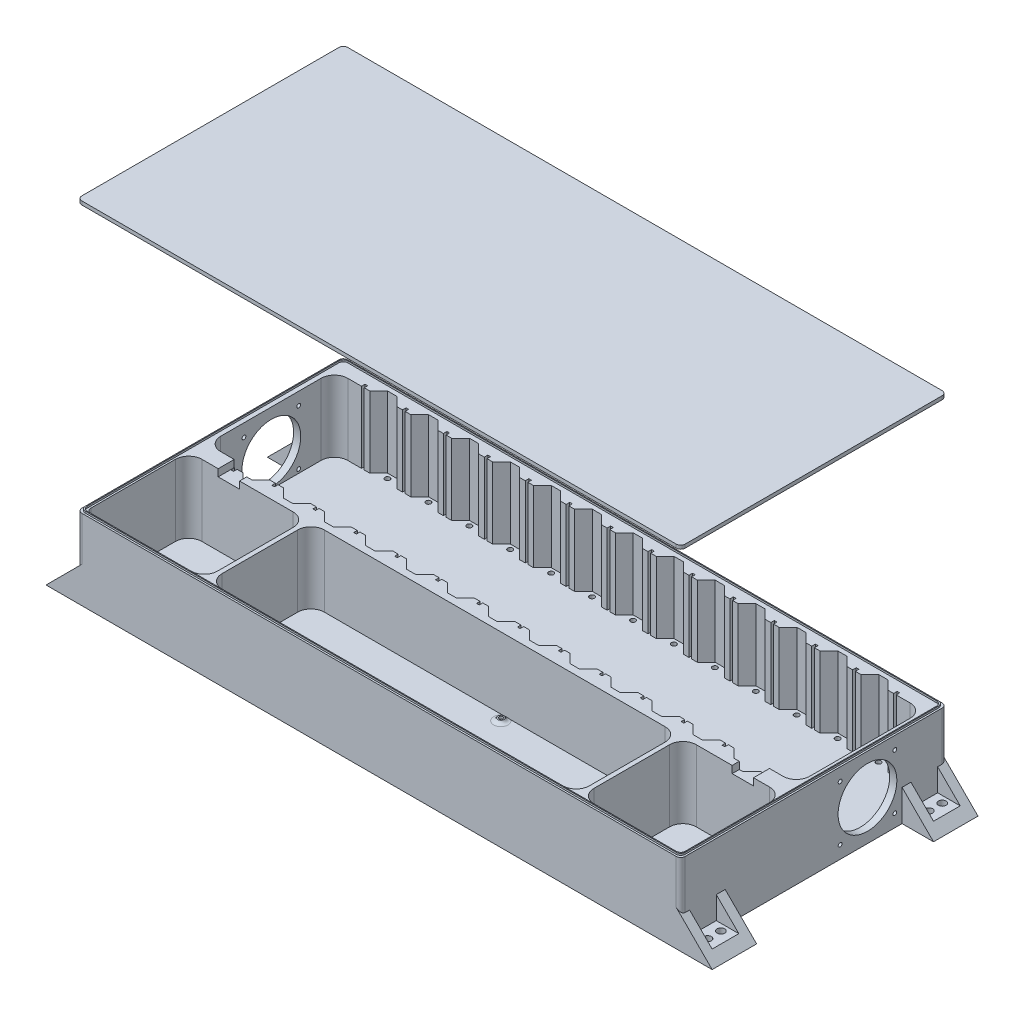
SolidWorks part; units mm, degrees
note: The reader was unsure of these and kept them because the rebuilt part matched: shared geometry of "Szkic1<8>", "Szkic1<9>", "Szkic3<4>".
ref_plane "Front Plane" through (0, 0, 0) normal (0, 0, 1) x (1, 0, 0)
ref_plane "Top Plane" through (0, 0, 0) normal (0, 1, 0) x (1, 0, 0)
ref_plane "Right Plane" through (0, 0, 0) normal (1, 0, 0) x (0, 0, -1)
sketch "Szkic1" plane through (0, 0, 0) normal (0, 1, 0) x (1, 0, 0)
  line L0 (6.5, 25) -> (-3.5, 15)
  line L1 (-11.5, 15) -> (34.5, 15)
  line L2 (-11.5, 15) -> (-11.5, -127)
  line L3 (-11.5, -127) -> (34.5, -127)
  line L4 (34.5, 15) -> (34.5, -127)
  line L5 (6.5, 15) -> (16.5, 15)
  line L6 (6.5, 15) -> (6.5, 25)
  line L7 (6.5, 25) -> (16.5, 25)
  line L8 (16.5, 15) -> (16.5, 25)
  line L9 (16.5, 25) -> (26.5, 15)
  line L10 (-11.5, 15.4) -> (-3.6657, 15.4)
  line L11 (-3.6657, 15.4) -> (6.3343, 25.4)
  line L12 (-11.5, -56) -> (-33.554, -56) construction
  line L13 (16.5, -137) -> (26.5, -127)
  line L14 (16.5, -127) -> (16.5, -137)
  line L15 (6.5, -127) -> (6.5, -137)
  line L16 (6.5, -137) -> (16.5, -137)
  line L17 (6.5, -137) -> (-3.5, -127)
  line L18 (-11.5, -155) -> (34.5, -155) [skipped]
  line L19 (-11.5, -183) -> (34.5, -183) [skipped]
  line L20 (6.3343, 25.4) -> (16.6657, 25.4)
  line L21 (16.6657, 25.4) -> (26.6657, 15.4)
  line L22 (26.6657, 15.4) -> (34.5, 15.4)
  line L23 (-11.5, 15.4) -> (-11.5, 15)
  line L24 (34.5, 15.4) -> (34.5, 15)
  line L25 (24.8809, -127.4) -> (34.5, -127.4)
  line L27 (6.3571, -137.4) -> (16.6894, -137.4)
  line L28 (-11.5, -127.4) -> (-5.8507, -127.4)
  line L30 (11.5, 15) -> (11.5, 25)
  line L31 (34.5, 15.4) -> (42.3343, 15.4)
  line L32 (42.3343, 15.4) -> (52.3343, 25.4)
  line L33 (52.3343, 25.4) -> (62.6657, 25.4)
  line L34 (62.6657, 25.4) -> (72.6657, 15.4)
  line L35 (72.6657, 15.4) -> (80.5, 15.4)
  line L36 (80.5, 15.4) -> (88.3343, 15.4)
  line L37 (88.3343, 15.4) -> (98.3343, 25.4)
  line L38 (98.3343, 25.4) -> (108.6657, 25.4)
  line L39 (108.6657, 25.4) -> (118.6657, 15.4)
  line L40 (118.6657, 15.4) -> (126.5, 15.4)
  line L41 (126.5, 15.4) -> (134.3343, 15.4)
  line L42 (134.3343, 15.4) -> (144.3343, 25.4)
  line L43 (144.3343, 25.4) -> (154.6657, 25.4)
  line L44 (154.6657, 25.4) -> (164.6657, 15.4)
  line L45 (164.6657, 15.4) -> (172.5, 15.4)
  line L46 (172.5, 15.4) -> (180.3343, 15.4)
  line L47 (180.3343, 15.4) -> (190.3343, 25.4)
  line L48 (190.3343, 25.4) -> (200.6657, 25.4)
  line L49 (200.6657, 25.4) -> (210.6657, 15.4)
  line L50 (210.6657, 15.4) -> (218.5, 15.4)
  line L51 (218.5, 15.4) -> (226.3343, 15.4)
  line L52 (226.3343, 15.4) -> (236.3343, 25.4)
  line L53 (236.3343, 25.4) -> (246.6657, 25.4)
  line L54 (246.6657, 25.4) -> (256.6657, 15.4)
  line L55 (256.6657, 15.4) -> (264.5, 15.4)
  line L56 (264.5, 15.4) -> (272.3343, 15.4)
  line L57 (272.3343, 15.4) -> (282.3343, 25.4)
  line L58 (282.3343, 25.4) -> (292.6657, 25.4)
  line L59 (292.6657, 25.4) -> (302.6657, 15.4)
  line L60 (302.6657, 15.4) -> (310.5, 15.4)
  line L61 (310.5, 15.4) -> (318.3343, 15.4)
  line L62 (318.3343, 15.4) -> (328.3343, 25.4)
  line L63 (328.3343, 25.4) -> (338.6657, 25.4)
  line L64 (338.6657, 25.4) -> (348.6657, 15.4)
  line L65 (348.6657, 15.4) -> (356.5, 15.4)
  line L66 (356.5, 15.4) -> (364.3343, 15.4)
  line L67 (364.3343, 15.4) -> (374.3343, 25.4)
  line L68 (374.3343, 25.4) -> (384.6657, 25.4)
  line L69 (384.6657, 25.4) -> (394.6657, 15.4)
  line L70 (394.6657, 15.4) -> (402.5, 15.4)
  line L71 (402.5, 15.4) -> (410.3343, 15.4)
  line L72 (410.3343, 15.4) -> (420.3343, 25.4)
  line L73 (420.3343, 25.4) -> (430.6657, 25.4)
  line L74 (430.6657, 25.4) -> (440.6657, 15.4)
  line L75 (440.6657, 15.4) -> (448.5, 15.4)
  line L76 (448.5, 15.4) -> (456.3343, 15.4)
  line L77 (456.3343, 15.4) -> (466.3343, 25.4)
  line L78 (466.3343, 25.4) -> (476.6657, 25.4)
  line L79 (476.6657, 25.4) -> (486.6657, 15.4)
  line L80 (486.6657, 15.4) -> (494.5, 15.4)
  line L81 (494.5, 15.4) -> (502.3343, 15.4)
  line L82 (502.3343, 15.4) -> (512.3343, 25.4)
  line L83 (512.3343, 25.4) -> (522.6657, 25.4)
  line L84 (522.6657, 25.4) -> (532.6657, 15.4)
  line L85 (532.6657, 15.4) -> (540.5, 15.4)
  line L86 (540.5, 15.4) -> (548.3343, 15.4)
  line L87 (548.3343, 15.4) -> (558.3343, 25.4)
  line L88 (558.3343, 25.4) -> (568.6657, 25.4)
  line L89 (568.6657, 25.4) -> (578.6657, 15.4)
  line L90 (578.6657, 15.4) -> (586.5, 15.4)
  line L91 (-11.5, -127.4) -> (-3.6657, -127.4)
  line L92 (-3.6657, -127.4) -> (6.3343, -137.4)
  line L93 (16.6657, -137.4) -> (26.6657, -127.4)
  line L94 (6.3343, -137.4) -> (16.6657, -137.4)
  line L95 (26.6657, -127.4) -> (34.5, -127.4)
  line L96 (310.5, -127.4) -> (318.3343, -127.4)
  line L97 (302.6657, -127.4) -> (310.5, -127.4)
  line L98 (292.6657, -137.4) -> (302.6657, -127.4)
  line L99 (282.3343, -137.4) -> (292.6657, -137.4)
  line L100 (272.3343, -127.4) -> (282.3343, -137.4)
  line L101 (264.5, -127.4) -> (272.3343, -127.4)
  line L102 (256.6657, -127.4) -> (264.5, -127.4)
  line L103 (246.6657, -137.4) -> (256.6657, -127.4)
  line L104 (236.3343, -137.4) -> (246.6657, -137.4)
  line L105 (226.3343, -127.4) -> (236.3343, -137.4)
  line L106 (218.5, -127.4) -> (226.3343, -127.4)
  line L107 (210.6657, -127.4) -> (218.5, -127.4)
  line L108 (200.6657, -137.4) -> (210.6657, -127.4)
  line L109 (190.3343, -137.4) -> (200.6657, -137.4)
  line L110 (180.3343, -127.4) -> (190.3343, -137.4)
  line L111 (172.5, -127.4) -> (180.3343, -127.4)
  line L112 (164.6657, -127.4) -> (172.5, -127.4)
  line L113 (154.6657, -137.4) -> (164.6657, -127.4)
  line L114 (144.3343, -137.4) -> (154.6657, -137.4)
  line L115 (134.3343, -127.4) -> (144.3343, -137.4)
  line L116 (126.5, -127.4) -> (134.3343, -127.4)
  line L117 (118.6657, -127.4) -> (126.5, -127.4)
  line L118 (108.6657, -137.4) -> (118.6657, -127.4)
  line L119 (98.3343, -137.4) -> (108.6657, -137.4)
  line L120 (88.3343, -127.4) -> (98.3343, -137.4)
  line L121 (80.5, -127.4) -> (88.3343, -127.4)
  line L122 (72.6657, -127.4) -> (80.5, -127.4)
  line L123 (62.6657, -137.4) -> (72.6657, -127.4)
  line L124 (52.3343, -137.4) -> (62.6657, -137.4)
  line L125 (42.3343, -127.4) -> (52.3343, -137.4)
  line L126 (34.5, -127.4) -> (42.3343, -127.4)
  line L127 (512.3343, -137.4) -> (522.6657, -137.4)
  line L128 (466.3343, -137.4) -> (476.6657, -137.4)
  line L129 (420.3343, -137.4) -> (430.6657, -137.4)
  line L130 (410.3343, -127.4) -> (420.3343, -137.4)
  line L131 (402.5, -127.4) -> (410.3343, -127.4)
  line L132 (394.6657, -127.4) -> (402.5, -127.4)
  line L133 (384.6657, -137.4) -> (394.6657, -127.4)
  line L134 (374.3343, -137.4) -> (384.6657, -137.4)
  line L135 (364.3343, -127.4) -> (374.3343, -137.4)
  line L136 (356.5, -127.4) -> (364.3343, -127.4)
  line L137 (348.6657, -127.4) -> (356.5, -127.4)
  line L138 (338.6657, -137.4) -> (348.6657, -127.4)
  line L139 (328.3343, -137.4) -> (338.6657, -137.4)
  line L140 (318.3343, -127.4) -> (328.3343, -137.4)
  line L141 (578.6657, -127.4) -> (586.5, -127.4)
  line L142 (568.6657, -137.4) -> (578.6657, -127.4)
  line L143 (558.3343, -137.4) -> (568.6657, -137.4)
  line L144 (548.3343, -127.4) -> (558.3343, -137.4)
  line L145 (540.5, -127.4) -> (548.3343, -127.4)
  line L146 (532.6657, -127.4) -> (540.5, -127.4)
  line L147 (522.6657, -137.4) -> (532.6657, -127.4)
  line L148 (502.3343, -127.4) -> (512.3343, -137.4)
  line L149 (494.5, -127.4) -> (502.3343, -127.4)
  line L150 (486.6657, -127.4) -> (494.5, -127.4)
  line L151 (586.5, 15.4) -> (586.5, -127.4)
  line L152 (-51.5, 33.4) -> (626.5, 33.4)
  line L153 (-51.5, 33.4) -> (-51.5, -145.4)
  line L154 (-51.5, -145.4) -> (626.5, -145.4)
  line L155 (626.5, 33.4) -> (626.5, -145.4)
  line L156 (586.5, -127.4) -> (626.5, -127.4)
  line L157 (586.5, 15.4) -> (626.5, 15.4)
  line L158 (-43.5, 15.4) -> (-43.5, -127.4)
  line L159 (618.5, 15.4) -> (618.5, -127.4)
  line L160 (586.5, -127.4) -> (586.5, -145.4)
  line L161 (-11.5, -127) -> (-11.5, -127.4)
  line L162 (-11.5, -127.4) -> (-51.5, -127.4)
  line L163 (-11.5, 15.4) -> (-51.5, 15.4)
  line L164 (476.6657, -137.4) -> (486.6657, -127.4)
  line L165 (456.3343, -127.4) -> (466.3343, -137.4)
  line L166 (448.5, -127.4) -> (456.3343, -127.4)
  line L167 (440.6657, -127.4) -> (448.5, -127.4)
  line L168 (430.6657, -137.4) -> (440.6657, -127.4)
  circle A0 centre (0, 0) radius 8.25
  circle A1 centre (0, 0) radius 10.6
  circle A2 centre (0, 0) radius 10.1
  circle A3 centre (0, 0) radius 11
  circle A5 centre (23, 0) radius 8.25
  circle A6 centre (23, 0) radius 10.6
  circle A7 centre (23, 0) radius 10.1
  circle A8 centre (23, 0) radius 11
  circle A10 centre (23, -28) radius 8.25
  circle A11 centre (23, -28) radius 10.6
  circle A12 centre (23, -28) radius 10.1
  circle A13 centre (23, -28) radius 11
  circle A15 centre (0, -28) radius 8.25
  circle A16 centre (0, -28) radius 10.6
  circle A17 centre (0, -28) radius 10.1
  circle A18 centre (0, -28) radius 11
  circle A20 centre (0, -56) radius 11
  circle A21 centre (0, -56) radius 10.6
  circle A22 centre (0, -56) radius 10.1
  circle A23 centre (0, -56) radius 8.25
  circle A24 centre (23, -56) radius 8.25
  circle A25 centre (23, -56) radius 10.1
  circle A26 centre (23, -56) radius 10.6
  circle A27 centre (23, -56) radius 11
  circle A28 centre (0, -84) radius 11
  circle A29 centre (0, -84) radius 10.6
  circle A30 centre (0, -84) radius 10.1
  circle A31 centre (0, -84) radius 8.25
  circle A32 centre (23, -84) radius 8.25
  circle A33 centre (23, -84) radius 10.1
  circle A34 centre (23, -84) radius 10.6
  circle A35 centre (23, -84) radius 11
  circle A36 centre (0, -112) radius 11
  circle A37 centre (0, -112) radius 10.6
  circle A38 centre (0, -112) radius 10.1
  circle A39 centre (0, -112) radius 8.25
  circle A40 centre (23, -112) radius 8.25
  circle A41 centre (23, -112) radius 10.1
  circle A42 centre (23, -112) radius 10.6
  circle A43 centre (23, -112) radius 11
  circle A44 centre (11.5, 20) radius 2.8
  circle A45 centre (11.5, -132) radius 2.8
  circle A46 centre (57.5, 20) radius 2.8
  circle A47 centre (103.5, 20) radius 2.8
  circle A48 centre (149.5, 20) radius 2.8
  circle A49 centre (195.5, 20) radius 2.8
  circle A50 centre (241.5, 20) radius 2.8
  circle A51 centre (287.5, 20) radius 2.8
  circle A52 centre (333.5, 20) radius 2.8
  circle A53 centre (379.5, 20) radius 2.8
  circle A54 centre (425.5, 20) radius 2.8
  circle A55 centre (471.5, 20) radius 2.8
  circle A56 centre (517.5, 20) radius 2.8
  circle A57 centre (563.5, 20) radius 2.8
  circle A58 centre (287.5, -132) radius 2.8
  circle A59 centre (241.5, -132) radius 2.8
  circle A60 centre (195.5, -132) radius 2.8
  circle A61 centre (149.5, -132) radius 2.8
  circle A62 centre (103.5, -132) radius 2.8
  circle A63 centre (57.5, -132) radius 2.8
  circle A64 centre (425.5, -132) radius 2.8
  circle A65 centre (379.5, -132) radius 2.8
  circle A66 centre (333.5, -132) radius 2.8
  circle A67 centre (563.5, -132) radius 2.8
  circle A68 centre (517.5, -132) radius 2.8
  circle A69 centre (471.5, -132) radius 2.8
  dimension "D1" = 16.5
  dimension "D2" = 20.2
  dimension "D3" = 21.2
  dimension "D4" = 0.4
  dimension "D5" = 23
  dimension "D8" = 11.5
  dimension "D10" = 2
  dimension "D22" = 5.6
  dimension "D9" = 11.5
  dimension "D11" = 15
  dimension "D12" = 10
  dimension "D13" = 18
  dimension "D14" = 10
  dimension "D15" = 3
  dimension "D16" = 15
  dimension "D17" = 0.4
  dimension "D18" = 45
  dimension "D19" = 45
  dimension "D20" = 0.4
  dimension "D21" = 0.4
  dimension "D23" = 0.4
  dimension "D25" = 0.4
  dimension "D26" = 40
  dimension "D27" = 40
  dimension "D28" = 8
  dimension "D29" = 8
  dimension "D6" = 2
  dimension "D7" = 2
extrude "Dodanie-wyciągnięcie1" add sketch "Szkic1" along normal blind 10
extrude "Dodanie-wyciągnięcie2" add sketch "Szkic1<8>" along normal blind 80 from surface at 10 starting at face at (287.5, 10, 56)
sketch "Szkic1<8>" plane through (0, 0, 0) normal (0, 1, 0) x (1, 0, 0) same geometry as "Szkic1"
extrude "Wytnij-wyciągnięcie2" cut sketch "Szkic1<9>" against normal blind 5 from surface contours A46 | A47 | A48 | A49 | A61 | A60 | A50 | A51 | A58 | A66 | A65 | A52 | A53 | A54 | A55 | A64 | A67 | A57 | A56
sketch "Szkic1<9>" plane through (0, 0, 0) normal (0, 1, 0) x (1, 0, 0) same geometry as "Szkic1"
sketch "Szkic2" plane through (-51.5, 0, 0) normal (-1, 0, 0) x (0, 0, 1)
  line L0 (-33.4, 0) -> (145.4, 0) construction
  circle A1 centre (24.7303, 75.747) radius 2.15
  circle A2 centre (24.7303, 14.247) radius 2.15
  circle A3 centre (86.2303, 14.247) radius 2.15
  circle A4 centre (86.2303, 75.747) radius 2.15
  circle A5 centre (55.4803, 44.997) radius 33.0377
  point P2 (56, 0)
  point P5 (22.0807, 90.9367)
  dimension "D3" = 43.4871
  dimension "D4" = 66.0755
  dimension "D1" = 43.4871
  dimension "D2" = 43.4871
  dimension "D5" = 43.4871
  dimension "D6" = 45
extrude "Wytnij-wyciągnięcie3" cut sketch "Szkic2" against normal blind 800
sketch "Szkic3" plane through (0, 0, 0) normal (0, -1, 0) x (1, 0, 0)
  line L0 (626.5, -33.4) -> (626.5, 145.4) construction
  line L1 (-51.5, 145.4) -> (626.5, 145.4)
  line L2 (-51.5, 145.4) -> (-51.5, 265.4)
  line L3 (-51.5, 265.4) -> (626.5, 265.4)
  line L4 (626.5, 145.4) -> (626.5, 265.4)
  line L5 (-46.5, 260.4) -> (621.5, 260.4)
  line L6 (-46.5, 260.4) -> (-46.5, 145.4)
  line L7 (-46.5, 145.4) -> (621.5, 145.4)
  line L8 (621.5, 260.4) -> (621.5, 145.4)
  line M6 (626.5, 145.4) -> (-51.5, 145.4)
  dimension "D1" = 120
  dimension "D2" = 5
  dimension "D3" = 0
  dimension "D4" = 5
  dimension "D5" = 5
extrude "Dodanie-wyciągnięcie3" add sketch "Szkic3" against normal up to surface (10 mm away) contours L5 L8 L4 L3 L2 L1 L6 M6 | L8 L5 L6 L1
extrude "Dodanie-wyciągnięcie4" add sketch "Szkic3<4>" against normal up to surface (90 mm away) contours L5 L8 L4 L3 L2 L1 L6 M6 up to face at (287.5, 90, 56)
sketch "Szkic3<4>" plane through (0, 0, 0) normal (0, -1, 0) x (1, 0, 0) same geometry as "Szkic3"
ref_plane "Płaszczyzna1" through (287.5, 0, 0) normal (-1, 0, 0) x (0, 0, 1)
sketch "Szkic5" plane through (0, 0, 265.4) normal (0, 0, 1) x (1, 0, 0)
  line L0 (-51.5, 0) -> (-86.8553, 0)
  line L1 (-86.8553, 0) -> (-51.5, 35.3553)
  line L2 (-51.5, 90) -> (-51.5, 0) construction
  line L3 (-51.5, 35.3553) -> (-51.5, 0)
  dimension "D1" = 50
extrude "Dodanie-wyciągnięcie5" add sketch "Szkic5" against normal blind 50
sketch "Szkic6" plane through (-51.5, 0, 0) normal (-1, 0, 0) x (0, 0, 1)
  line L0 (215.4, 35.3553) -> (265.4, 35.3553) construction
  line L1 (225.4, 35.3553) -> (255.4, 35.3553)
  line L2 (225.4, 35.3553) -> (225.4, 10)
  line L3 (225.4, 10) -> (255.4, 10)
  line L4 (255.4, 35.3553) -> (255.4, 10)
  line L5 (215.4, 35.3553) -> (215.4, 0) construction
  line L6 (265.4, 35.3553) -> (265.4, 0) construction
  line L7 (215.4, 0) -> (265.4, 0) construction
  dimension "D1" = 10
  dimension "D2" = 10
  dimension "D3" = 10
extrude "Wytnij-wyciągnięcie4" cut sketch "Szkic6" along normal blind 40
sketch "Szkic7" plane through (0, 10, 0) normal (0, 1, 0) x (1, 0, 0)
  line L0 (-64.1777, -255.4) -> (-64.1777, -225.4)
  line L1 (-76.8553, -255.4) -> (-51.5, -255.4) construction
  line L3 (-59.9277, -240.4) -> (-59.9277, -225.4)
  line L4 (-59.9277, -240.4) -> (-59.9277, -255.4)
  line L6 (-51.5, -255.4) -> (-76.8553, -255.4) construction
  circle A3 centre (-64.1777, -232.9) radius 4.25
  circle A4 centre (-64.1777, -247.9) radius 4.25
  dimension "D1" = 8.5
  dimension "D2" = 8.5
extrude "Wytnij-wyciągnięcie5" cut sketch "Szkic7" against normal blind 40 contours L0 A4 | L0 A4 | L0 A3 | L0 A3
ref_plane "Płaszczyzna2" through (0, 0, 116) normal (0, 0, 1) x (1, 0, 0)
mirror "Lustro1" about plane through (287.5, 0, 0) normal (-1, 0, 0) of "Wytnij-wyciągnięcie4", "Dodanie-wyciągnięcie5", "Wytnij-wyciągnięcie5" second plane through (0, 0, 116) second plane normal (0, 0, 1)
sketch "Szkic9" plane through (0, 10, 0) normal (0, 1, 0) x (1, 0, 0)
  line L0 (506.5, -145.4) -> (506.5, -260.4)
  line L1 (621.5, -145.4) -> (-46.5, -145.4) construction
  line L2 (621.5, -260.4) -> (-46.5, -260.4) construction
  line L3 (88.5, -145.4) -> (88.5, -260.4)
  line L4 (621.5, -145.4) -> (-46.5, -145.4) construction
  line L5 (621.5, -260.4) -> (-46.5, -260.4) construction
  line L6 (-51.5, -265.4) -> (-51.5, 33.4) construction
  line L7 (626.5, -265.4) -> (626.5, 33.4) construction
  dimension "D1" = 140
  dimension "D2" = 120
extrude "Wyciągnięcie-cienka ścianka1" add sketch "Szkic9" along normal up to surface (80 mm away) thin up to face at (287.5, 90, 202.9) thin type mid plane wall 5
sketch "Szkic8" plane through (0, 10, 0) normal (0, 1, 0) x (1, 0, 0)
  circle A0 centre (452.5969, -151.7073) radius 2.1
  circle A1 centre (452.6219, -219.6823) radius 2.1
  circle A2 centre (310.9469, -151.9823) radius 2.1
  circle A3 centre (310.4051, -200.749) radius 2.1
  circle A4 centre (331.8636, -254.5905) radius 2.1
  circle A5 centre (310.9469, -151.9823) radius 3.5
  circle A6 centre (452.5969, -151.7073) radius 3.5
  circle A7 centre (452.6219, -219.6823) radius 3.5
  circle A8 centre (331.8636, -254.5905) radius 3.5
  circle A9 centre (310.4051, -200.749) radius 3.5
  dimension "D1" = 7
  dimension "D2" = 7
  dimension "D3" = 7
  dimension "D4" = 7
  dimension "D5" = 7
  dimension "D6" = 4.2
  dimension "D7" = 4.2
  dimension "D8" = 4.2
  dimension "D9" = 4.2
  dimension "D10" = 4.2
extrude "Dodanie-wyciągnięcie6" add sketch "Szkic8" along normal blind 3
fillet "Zaokrąglenie2" radius 5 5 edges at (331.8636, 10, 258.0905) (452.6219, 10, 223.1823) (452.5969, 10, 155.2073) (310.4051, 10, 204.249) (310.9469, 10, 155.4823)
sketch "Szkic10" plane through (0, 90, 0) normal (0, 1, 0) x (1, 0, 0)
  line L0 (-49, 30.9) -> (624, 30.9)
  line L2 (624, 30.9) -> (624, -262.9)
  line L3 (624, -262.9) -> (-49, -262.9)
  line L4 (-49, -262.9) -> (-49, 30.9)
  line L5 (626.5, 33.4) -> (-51.5, 33.4) construction
  line L6 (-51.5, -265.4) -> (-51.5, 33.4) construction
  line L7 (-51.5, -265.4) -> (626.5, -265.4) construction
  line L8 (626.5, -265.4) -> (626.5, 33.4) construction
  point P0 (624.4868, 27.7695)
  point P4 (0, 0)
  point P7 (-49.386, 27.672)
  dimension "D1" = 2.5
  dimension "D2" = 2.5
  dimension "D3" = 2.5
  dimension "D4" = 2.5
extrude "Wyciągnięcie-cienka ścianka2" add sketch "Szkic10" along normal blind 2 thin thin type mid plane wall 1
sketch "Szkic14" plane through (0, 90, 0) normal (0, 1, 0) x (1, 0, 0)
  line L0 (34.5, 15.4) -> (34.5, 19.4)
  line L1 (42.3343, 15.4) -> (26.6657, 15.4) construction
  line L2 (80.5, 15.4) -> (80.5, 19.4)
  line L3 (126.5, 15.4) -> (126.5, 19.4)
  line L4 (172.5, 15.4) -> (172.5, 19.4)
  line L5 (218.5, 15.4) -> (218.5, 19.4)
  line L6 (264.5, 15.4) -> (264.5, 19.4)
  line L7 (310.5, 15.4) -> (310.5, 19.4)
  line L8 (356.5, 15.4) -> (356.5, 19.4)
  line L9 (402.5, 15.4) -> (402.5, 19.4)
  line L10 (448.5, 15.4) -> (448.5, 19.4)
  line L11 (494.5, 15.4) -> (494.5, 19.4)
  line L12 (540.5, 15.4) -> (540.5, 19.4)
  line L13 (586.5, 15.4) -> (586.5, 19.4)
  line L14 (-11.5, 15.4) -> (-11.5, 19.4)
  line L15 (-43.5, -56) -> (-26.8479, -56) construction
  line L16 (-43.5, -127.4) -> (-43.5, 15.4) construction
  line L17 (-11.5, -127.4) -> (-11.5, -131.4)
  line L18 (586.5, -127.4) -> (586.5, -131.4)
  line L19 (540.5, -127.4) -> (540.5, -131.4)
  line L20 (494.5, -127.4) -> (494.5, -131.4)
  line L21 (448.5, -127.4) -> (448.5, -131.4)
  line L22 (402.5, -127.4) -> (402.5, -131.4)
  line L23 (356.5, -127.4) -> (356.5, -131.4)
  line L24 (310.5, -127.4) -> (310.5, -131.4)
  line L25 (264.5, -127.4) -> (264.5, -131.4)
  line L26 (218.5, -127.4) -> (218.5, -131.4)
  line L27 (172.5, -127.4) -> (172.5, -131.4)
  line L28 (126.5, -127.4) -> (126.5, -131.4)
  line L29 (80.5, -127.4) -> (80.5, -131.4)
  line L30 (34.5, -127.4) -> (34.5, -131.4)
  dimension "D1" = 4
  dimension "D2" = 13
  dimension "D3" = 2
extrude "Wycięcie-wyciągnięcie-cienka ścianka2" cut sketch "Szkic14" against normal up to surface (80 mm away) thin thin type mid plane wall 3
ref_plane "Płaszczyzna3" through (0, 390, 0) normal (0, 1, 0) x (1, 0, 0)
sketch "Szkic11" plane through (0, 390, 0) normal (0, 1, 0) x (1, 0, 0)
  line L1 (-51.5, 33.4) -> (626.5, 33.4)
  line L2 (-51.5, 33.4) -> (-51.5, -265.4)
  line L3 (-51.5, -265.4) -> (626.5, -265.4)
  line L4 (626.5, 33.4) -> (626.5, -265.4)
extrude "Dodanie-wyciągnięcie7" add sketch "Szkic11" along normal blind 4 separate body
sketch "Szkic12" plane through (0, 390, 0) normal (0, 1, 0) x (1, 0, 0)
  line L0 (-49, 30.9) -> (624, 30.9)
  line L2 (624, 30.9) -> (624, -262.9)
  line L3 (624, -262.9) -> (-49, -262.9)
  line L4 (-49, -262.9) -> (-49, 30.9)
  point P0 (624.4868, 27.7695)
  point P4 (0, 0)
  point P7 (-49.386, 27.672)
extrude "Wycięcie-wyciągnięcie-cienka ścianka1" cut sketch "Szkic12" along normal blind 2 thin thin type mid plane wall 1.2
fillet "Zaokrąglenie3" radius 5 14 edges at (626.5, 62.6777, 265.4) (624.5, 91, 263.4) (623.5, 91, 262.4) (623.5, 91, -30.4) (626.5, 62.6777, -33.4) (624.5, 91, -31.4) (-49.5, 91, -31.4) (-48.5, 91, -30.4) (-51.5, 62.6777, -33.4) (-51.5, 62.6777, 265.4) (-49.5, 91, 263.4) (-48.5, 91, 262.4) (621.5, 50, 260.4) (-46.5, 50, 260.4)
fillet "Zaokrąglenie4" radius 5 12 edges at (626.5, 392, 265.4) (624.6, 391, 263.5) (623.4, 391, 262.3) (623.4, 391, -30.3) (624.6, 391, -31.5) (626.5, 392, -33.4) (-51.5, 392, -33.4) (-48.4, 391, -30.3) (-49.6, 391, -31.5) (-48.4, 391, 262.3) (-49.6, 391, 263.5) (-51.5, 392, 265.4)
fillet "Zaokrąglenie5" radius 15 14 edges at (-43.5, 50, -15.4) (-43.5, 50, 127.4) (618.5, 50, 127.4) (618.5, 50, -15.4) (86, 50, 260.4) (91, 50, 260.4) (86, 50, 145.4) (91, 50, 145.4) (504, 50, 145.4) (504, 50, 260.4) (509, 50, 260.4) (509, 50, 145.4) (621.5, 50, 145.4) (-46.5, 50, 145.4)
sketch "Szkic13" plane through (0, 0, 145.4) normal (0, 0, 1) x (1, 0, 0)
  line L0 (-44.5, 92) -> (619.5, 92) construction
  line L1 (564.3343, 92) -> (588.3343, 92)
  line L2 (564.3343, 92) -> (564.3343, 82)
  line L3 (564.3343, 82) -> (588.3343, 82)
  line L4 (588.3343, 92) -> (588.3343, 82)
  line L5 (548.3343, 90) -> (548.3343, 10) construction
  line L6 (287.5, 49.5) -> (287.5, -49.5) construction
  line L7 (-13.3343, 92) -> (-13.3343, 82)
  line L8 (10.6657, 82) -> (-13.3343, 82)
  line L9 (10.6657, 92) -> (10.6657, 82)
  line L10 (10.6657, 92) -> (-13.3343, 92)
  dimension "D1" = 16
  dimension "D2" = 10
  dimension "D3" = 24
extrude "Wytnij-wyciągnięcie7" cut sketch "Szkic13" against normal blind 30
